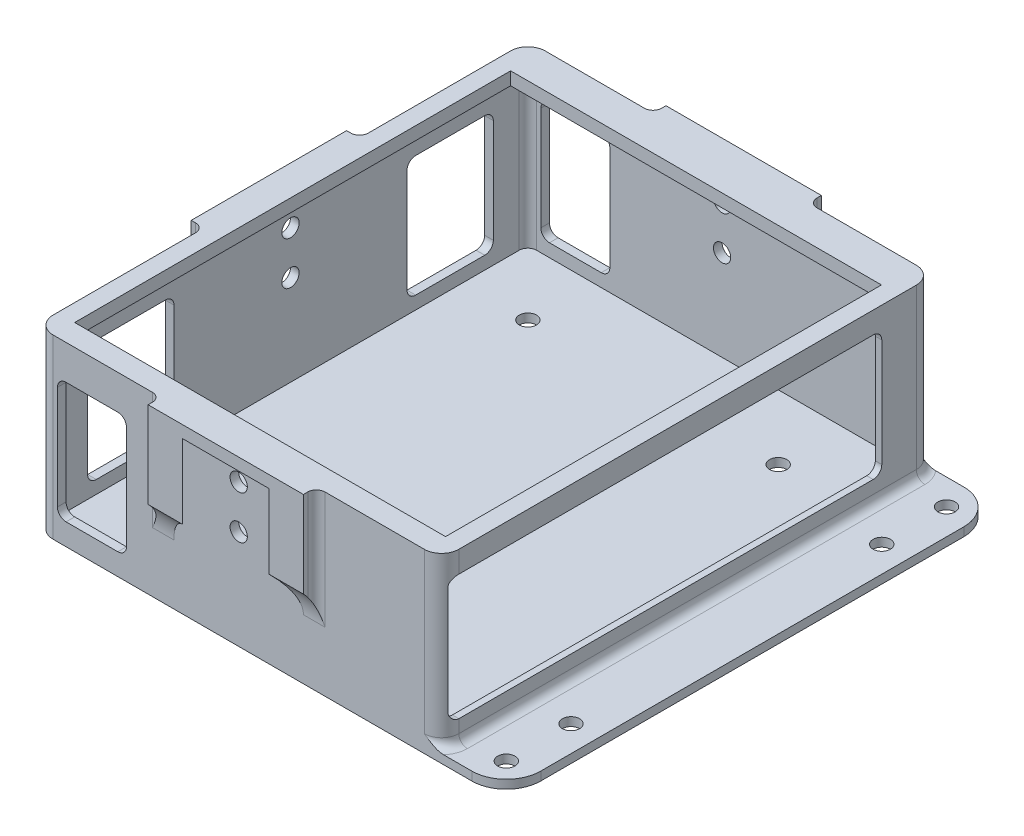
SolidWorks part; units mm, degrees
ref_plane "前视基准面" through (0, 0, 0) normal (0, 0, 1) x (1, 0, 0)
ref_plane "上视基准面" through (0, 0, 0) normal (0, 1, 0) x (1, 0, 0)
ref_plane "右视基准面" through (0, 0, 0) normal (1, 0, 0) x (0, 0, -1)
sketch "草图1" plane through (0, 0, 0) normal (0, 1, 0) x (1, 0, 0)
  line L1 (0, 0) -> (100, 0)
  line L2 (0, 0) -> (0, 130)
  line L3 (0, 130) -> (100, 130)
  line L4 (100, 0) -> (100, 130)
  circle A0 centre (15, 105) radius 2
  circle A1 centre (15, 19) radius 2
  circle A2 centre (73, 105) radius 2
  circle A3 centre (73, 19) radius 2
  dimension "D6" = 4
  dimension "D7" = 4
  dimension "D8" = 4
  dimension "D9" = 4
  dimension "D1" = 130
  dimension "D2" = 100
  dimension "D3" = 86
  dimension "D4" = 86
  dimension "D5" = 58
  dimension "D10" = 15
  dimension "D11" = 25
extrude "凸台-拉伸1" add sketch "草图1" along normal blind 2
sketch "草图3" plane through (0, 2, 0) normal (0, 1, 0) x (1, 0, 0)
  line L5 (0, 122) -> (0, 120)
  line L6 (100, 120) -> (0, 120)
  line L7 (100, 122) -> (100, 120)
  line L8 (100, 122) -> (0, 122)
  line L9 (100, 65) -> (6.6451, 65) construction
  line L10 (100, 8) -> (0, 8)
  line L11 (100, 8) -> (100, 10)
  line L12 (100, 10) -> (0, 10)
  line L13 (0, 8) -> (0, 10)
  line L18 (100, 0) -> (100, 130) construction
  line L20 (0, 130) -> (0, 0) construction
  dimension "D1" = 110
  dimension "D2" = 2
extrude "凸台-拉伸2" add sketch "草图3" along normal blind 39
sketch "草图4" plane through (0, 2, 0) normal (0, 1, 0) x (1, 0, 0)
  line L0 (0, 120) -> (100, 120) construction
  line L1 (90.5, 120) -> (92, 120)
  line L2 (90.5, 120) -> (90.5, 10)
  line L3 (90.5, 10) -> (92, 10)
  line L4 (92, 120) -> (92, 10)
  line L5 (100, 10) -> (0, 10) construction
  line L6 (100, 10) -> (100, 120) construction
  dimension "D1" = 8
  dimension "D2" = 1.5
extrude "凸台-拉伸3" add sketch "草图4" along normal blind 5
sketch "草图5" plane through (0, 0, 0) normal (-1, 0, 0) x (0, 0, 1)
  line L0 (-8, 41) -> (-8, 2) construction
  line L1 (-122, 41) -> (-8, 41)
  line L2 (-122, 41) -> (-122, 0)
  line L3 (-122, 0) -> (-8, 0)
  line L4 (-8, 41) -> (-8, 0)
  line L5 (-130, 0) -> (0, 0) construction
extrude "凸台-拉伸7" add sketch "草图5" along normal blind 2 contours L1 L4 L3 L2
sketch "草图6" plane through (0, 2, 0) normal (0, 1, 0) x (1, 0, 0)
  line L0 (92, 10) -> (92, 120) construction
  line L1 (0, 8) -> (92, 8)
  line L2 (0, 8) -> (0, 0)
  line L3 (0, 0) -> (100, 0)
  line L4 (100, 13) -> (100, 0)
  line L5 (0, 122) -> (92, 122)
  line L6 (0, 122) -> (0, 130)
  line L7 (0, 130) -> (100, 130)
  line L8 (100, 117) -> (100, 130)
  line L10 (100, 13) -> (100, 117)
  line L12 (92, 8) -> (92, 122)
extrude "切除-拉伸3" cut sketch "草图6" against normal through all and the other way through all
sketch "草图7" plane through (0, 41, 0) normal (0, 1, 0) x (1, 0, 0)
  line L0 (-2, 65) -> (-36.1179, 65) construction
  line L1 (-2, 122) -> (-2, 8) construction
  line L2 (45, 122) -> (45, 8) construction
  line L4 (-2, 8) -> (92, 8) construction
  line L5 (27, 8) -> (30, 8)
  line L6 (60, 8) -> (55, 5)
  line L7 (55, 5) -> (63, 5)
  line L8 (63, 5) -> (63, 8)
  line L9 (63, 8) -> (60, 8)
  line L10 (27, 5) -> (27, 8)
  line L11 (35, 5) -> (27, 5)
  line L12 (30, 8) -> (35, 5)
  line L13 (92, 122) -> (-2, 122) construction
  line L14 (30, 122) -> (35, 125)
  line L15 (35, 125) -> (27, 125)
  line L16 (27, 125) -> (27, 122)
  line L17 (63, 122) -> (60, 122)
  line L18 (63, 125) -> (63, 122)
  line L19 (55, 125) -> (63, 125)
  line L20 (60, 122) -> (55, 125)
  line L21 (27, 122) -> (30, 122)
  line L22 (-2, 80) -> (-5, 75)
  line L23 (-5, 75) -> (-5, 83)
  line L24 (-5, 83) -> (-2, 83)
  line L25 (-2, 83) -> (-2, 80)
  line L26 (-2, 47) -> (-2, 50)
  line L27 (-5, 47) -> (-2, 47)
  line L28 (-5, 55) -> (-5, 47)
  line L29 (-2, 50) -> (-5, 55)
  dimension "D1" = 15
  dimension "D2" = 3
  dimension "D3" = 3
  dimension "D4" = 10
  dimension "D5" = 10
  dimension "D6" = 15
  dimension "D7" = 3
  dimension "D8" = 3
extrude "凸台-拉伸8" add sketch "草图7" against normal blind 20
sketch "草图8" plane through (0, 41, 0) normal (0, 1, 0) x (1, 0, 0)
  line L0 (27, 122) -> (-2, 122) construction
  line L1 (27, 5) -> (63, 5)
  line L2 (27, 5) -> (27, 8)
  line L3 (27, 8) -> (63, 8)
  line L4 (63, 5) -> (63, 8)
  line L5 (63, 125) -> (27, 125)
  line L6 (63, 125) -> (63, 122)
  line L7 (63, 122) -> (27, 122)
  line L8 (27, 125) -> (27, 122)
  line L10 (-2, 83) -> (-5, 83)
  line L11 (-2, 83) -> (-2, 47)
  line L12 (-2, 47) -> (-5, 47)
  line L13 (-5, 83) -> (-5, 47)
extrude "凸台-拉伸9" add sketch "草图8" against normal blind 2.8
sketch "草图11" plane through (92, 0, 0) normal (1, 0, 0) x (0, 0, -1)
  line L0 (122, 0) -> (122, 41) construction
  line L1 (8, 41) -> (122, 41)
  line L2 (8, 41) -> (8, 36)
  line L3 (8, 36) -> (110, 36)
  line L4 (122, 41) -> (122, 36)
  line L6 (122, 0) -> (110, 0)
  line L7 (122, 0) -> (122, 36)
  line L9 (110, 0) -> (110, 36)
  dimension "D1" = 5
  dimension "D2" = 12
extrude "凸台-拉伸10" add sketch "草图11" against normal blind 1.5
fillet "圆角1" radius 10 6 edges at (61.5, 21, -122) (28.5, 21, -122) (-2, 21, -81.5) (-2, 21, -48.5) (61.5, 21, -8) (28.5, 21, -8)
sketch "草图12" plane through (0, 0, -8) normal (0, 0, 1) x (1, 0, 0)
  line L0 (45, 38.2) -> (45, -6.4511) construction
  line L1 (60, 38.2) -> (30, 38.2) construction
  line L2 (27, 41) -> (63, 41) construction
  circle A0 centre (45, 33) radius 2
  circle A1 centre (45, 23) radius 2
  dimension "D1" = 4
  dimension "D2" = 4
  dimension "D4" = 10
  dimension "D3" = 8
extrude "切除-拉伸4" cut sketch "草图12" against normal through all
sketch "草图13" plane through (-2, 0, 0) normal (-1, 0, 0) x (0, 0, 1)
  line L0 (-65, 38.2) -> (-65, 6.4815) construction
  line L1 (-50, 38.2) -> (-80, 38.2) construction
  line L4 (-83, 41) -> (-47, 41) construction
  circle A0 centre (-65, 33) radius 2
  circle A1 centre (-65, 23) radius 2
  dimension "D1" = 10
  dimension "D3" = 4
  dimension "D4" = 4
  dimension "D2" = 8
extrude "切除-拉伸5" cut sketch "草图13" against normal up to next
sketch "草图15" plane through (0, 0, -8) normal (0, 0, 1) x (1, 0, 0)
  line L0 (-2, 0) -> (92, 0) construction
  line L1 (3, 33) -> (19, 33)
  line L2 (3, 33) -> (3, 5)
  line L3 (3, 5) -> (19, 5)
  line L4 (19, 33) -> (19, 5)
  line L5 (-2, 41) -> (-2, 0) construction
  dimension "D1" = 16
  dimension "D2" = 28
  dimension "D3" = 5
  dimension "D4" = 5
extrude "切除-拉伸6" cut sketch "草图15" against normal through all
sketch "草图16" plane through (-2, 0, 0) normal (-1, 0, 0) x (0, 0, 1)
  line L0 (-65, 0) -> (-65, 63.4231) construction
  line L1 (-122, 0) -> (-8, 0) construction
  line L2 (-8, 41) -> (-8, 0) construction
  line L3 (-38, 5) -> (-18, 5)
  line L4 (-38, 5) -> (-38, 33)
  line L5 (-38, 33) -> (-18, 33)
  line L6 (-18, 5) -> (-18, 33)
  line L7 (-112, 5) -> (-112, 33)
  line L8 (-92, 33) -> (-112, 33)
  line L9 (-92, 5) -> (-92, 33)
  line L10 (-92, 5) -> (-112, 5)
  dimension "D1" = 20
  dimension "D2" = 28
  dimension "D3" = 5
  dimension "D4" = 10
extrude "切除-拉伸7" cut sketch "草图16" against normal up to next
fillet "圆角2" radius 2 28 edges at (91.25, 36, -10) (91.25, 7, -10) (91.25, 36, -110) (91.25, 7, -110) (27, 27.4293, -122) (63, 27.4293, -122) (63, 27.4293, -8) (27, 27.4293, -8) (-2, 27.4293, -47) (-2, 27.4293, -83) (19, 33, -121) (3, 33, -121) (3, 5, -121) (19, 5, -121) (-1, 33, -112) (-1, 33, -92) (-1, 5, -92) (-1, 5, -112) (19, 33, -9) (3, 33, -9) (19, 5, -9) (3, 5, -9) (-1, 33, -38) (-1, 33, -18) (-1, 5, -18) (-1, 5, -38) (0, 21.5, -10) (0, 21.5, -120)
sketch "草图14" plane through (0, 2, 0) normal (0, 1, 0) x (1, 0, 0)
  line L0 (92, 122) -> (65, 122) construction
  line L1 (92, 8) -> (99, 8)
  line L2 (92, 8) -> (92, 122)
  line L3 (92, 122) -> (99, 122)
  line L4 (107, 16) -> (107, 114)
  line L5 (107, 65) -> (70.1762, 65) construction
  line L6 (101, 14) -> (101, 38.1709) construction
  line L7 (101, 116) -> (101, 91.8291) construction
  arc A0 (99, 122) -> (107, 114) centre (99, 114) cw
  arc A1 (99, 8) -> (107, 16) centre (99, 16) ccw
  circle A2 centre (101, 14) radius 2
  circle A3 centre (101, 29) radius 2
  circle A4 centre (101, 101) radius 2
  circle A5 centre (101, 116) radius 2
  point P9 (107, 122)
  dimension "D2" = 8
  dimension "D3" = 4
  dimension "D4" = 4
  dimension "D5" = 15
  dimension "D6" = 72
  dimension "D1" = 15
  dimension "D7" = 6
extrude "凸台-拉伸11" add sketch "草图14" against normal blind 2
sketch "草图17" plane through (0, 41, 0) normal (0, 1, 0) x (1, 0, 0)
  line L1 (-2, 122) -> (91.9258, 122)
  line L3 (2, 114) -> (87.9258, 114)
  line L5 (-2, 8) -> (-2, 122)
  line L6 (-2, 8) -> (91.9258, 8)
  line L8 (2, 13) -> (87.9258, 13)
  line L10 (2, 13) -> (2, 114)
  line L11 (91.9258, 8) -> (91.9258, 122)
  line L12 (87.9258, 13) -> (87.9258, 114)
  dimension "D1" = 8
  dimension "D2" = 5
  dimension "D3" = 4
  dimension "D4" = 4
extrude "凸台-拉伸12" add sketch "草图17" against normal blind 3
fillet "圆角3" radius 4 4 edges at (-2, 20.5, -8) (-2, 20.5, -122) (92, 21.5, -8) (92, 21.5, -122)
fillet "圆角4" radius 2 3 edges at (90.8284, 2, -120.8284) (90.8284, 2, -9.1716) (92, 2, -65)
